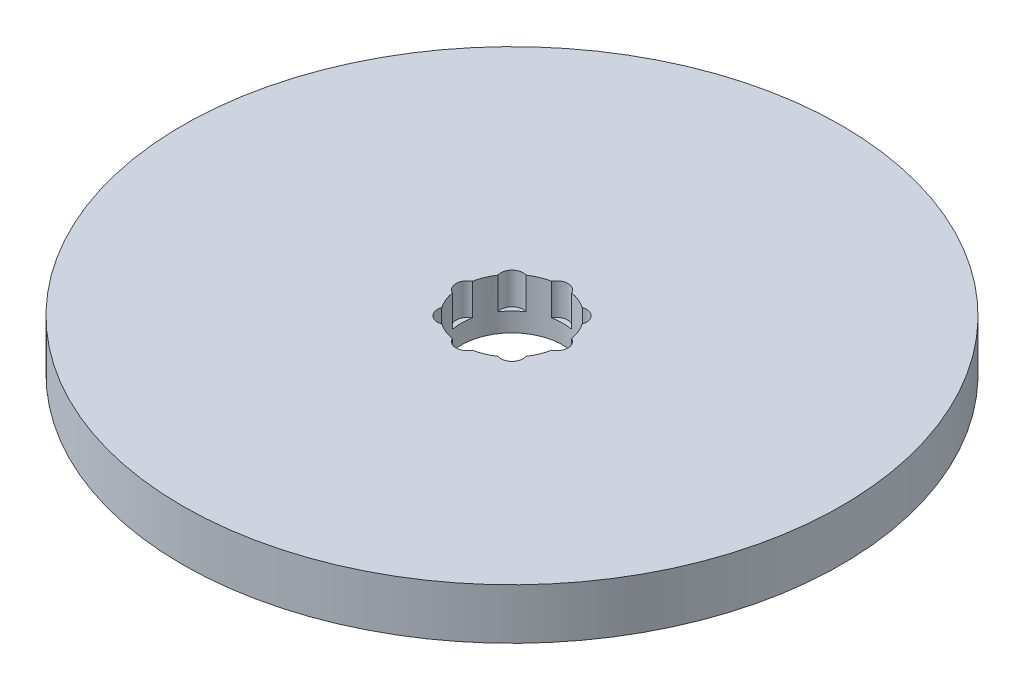
SolidWorks part; units mm, degrees
ref_plane "Front Plane" through (0, 0, 0) normal (0, 0, 1) x (1, 0, 0)
ref_plane "Top Plane" through (0, 0, 0) normal (0, 1, 0) x (1, 0, 0)
ref_plane "Right Plane" through (0, 0, 0) normal (1, 0, 0) x (0, 0, -1)
sketch "Sketch1" plane through (0, 0, 0) normal (0, 1, 0) x (1, 0, 0)
  circle A0 centre (0, 0) radius 65
  dimension "FLANGE_OD" = 130
extrude "Boss-Extrude1" add sketch "Sketch1" along normal blind 10
sketch "Sketch2" plane through (0, 0, 0) normal (0, 1, 0) x (1, 0, 0)
  circle A0 centre (0, 0) radius 10
  dimension "BORE_D" = 20
extrude "Cut-Extrude1" cut sketch "Sketch2" along normal through all
sketch "Sketch3" plane through (0, 10, 0) normal (0, 1, 0) x (1, 0, 0)
  circle A0 centre (0, 0) radius 8.8183 construction
  circle A1 centre (-8.8183, 0) radius 2.2082
  dimension "BOLT_D" = 4.4164
  dimension "BOLT_PCD" = 17.6366
extrude "Cut-Extrude2" cut sketch "Sketch3" against normal blind 6.2597
pattern_circular "CirPattern1" count 8 over 360 about axis through (0, 0, 0) along (0, 1, 0) of "Cut-Extrude2"
